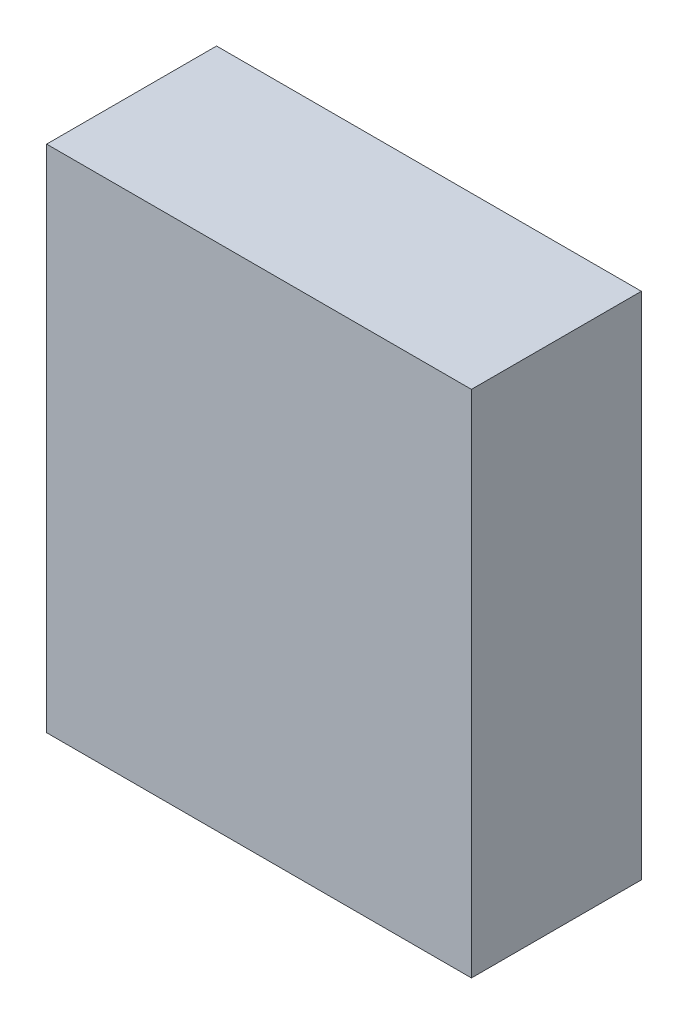
SolidWorks part; units mm, degrees
ref_plane "Front Plane" through (0, 0, 0) normal (0, 0, 1) x (1, 0, 0)
ref_plane "Top Plane" through (0, 0, 0) normal (0, 1, 0) x (1, 0, 0)
ref_plane "Right Plane" through (0, 0, 0) normal (1, 0, 0) x (0, 0, -1)
other "Center of Mass"
sketch "Sketch1" plane through (0, 0, 0) normal (0, 0, 1) x (1, 0, 0)
  line L1 (-125, -150) -> (125, -150)
  line L2 (-125, -150) -> (-125, 150)
  line L3 (-125, 150) -> (125, 150)
  line L4 (125, -150) -> (125, 150)
  line L5 (-125, -150) -> (125, 150) construction
  line L6 (-125, 150) -> (125, -150) construction
  point P0 (0, 0)
  dimension "D1" = 300
  dimension "D2" = 250
extrude "Boss-Extrude1" add sketch "Sketch1" along normal blind 100
sketch "Sketch2" plane through (0, 0, 0) normal (0, 0, -1) x (-1, 0, 0)
  line L0 (0, -100) -> (0, 100)
  line L1 (7.5, 92.5) -> (-7.5, 92.5)
  line L2 (7.5, 92.5) -> (7.5, 107.5)
  line L3 (7.5, 107.5) -> (-7.5, 107.5)
  line L4 (-7.5, 92.5) -> (-7.5, 107.5)
  line L5 (7.5, 92.5) -> (-7.5, 107.5) construction
  line L6 (7.5, 107.5) -> (-7.5, 92.5) construction
  line L7 (7.5, -107.5) -> (-7.5, -107.5)
  line L8 (7.5, -107.5) -> (7.5, -92.5)
  line L9 (7.5, -92.5) -> (-7.5, -92.5)
  line L10 (-7.5, -107.5) -> (-7.5, -92.5)
  line L11 (7.5, -107.5) -> (-7.5, -92.5) construction
  line L12 (7.5, -92.5) -> (-7.5, -107.5) construction
  point P0 (0, 100)
  point P5 (0, -100)
  point P14 (0, 0)
  dimension "D1" = 15
  dimension "D2" = 200
extrude "Boss-Extrude2" add sketch "Sketch2" along normal blind 7.5 contours L10 L7 L8 L9 | L4 L1 L2 L3 region at (3.75, 92.7121, 0) region at (-3.75, -92.7121, 0)
fillet "Fillet1" radius 7.5 4 edges at (0, 107.5, -7.5) (0, 92.5, -7.5) (0, -107.5, -7.5) (0, -92.5, -7.5)
